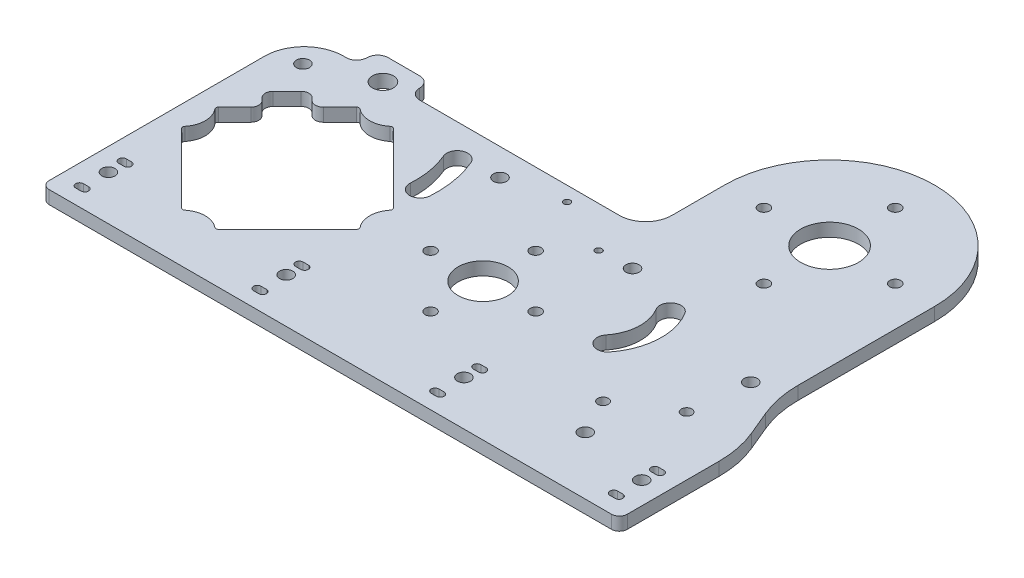
SolidWorks part; units mm, degrees
material "6061 Alloy"
ref_plane "Front Plane" through (0, 0, 0) normal (0, 0, 1) x (1, 0, 0)
ref_plane "Top Plane" through (0, 0, 0) normal (0, 1, 0) x (1, 0, 0)
ref_plane "Right Plane" through (0, 0, 0) normal (1, 0, 0) x (0, 0, -1)
sketch "Sketch1" plane through (0, 0, 0) normal (0, 1, 0) x (1, 0, 0)
  line L0 (0, 0) -> (190, 0)
  line L1 (210, 70) -> (210, 130)
  line L2 (130, 130) -> (130, 110)
  line L3 (120, 100) -> (15, 100)
  line L4 (0, 85) -> (0, 0)
  line L5 (41.3, 81.8789) -> (41.3, 71.8789) construction
  line L6 (41.3, 71.8789) -> (41.3, 52.3789) construction
  line L7 (41.3, 52.3789) -> (8.8, 52.3789) construction
  line L8 (17.63, 76.0489) -> (64.97, 76.0489) construction
  line L9 (17.63, 76.0489) -> (17.63, 28.7089) construction
  line L10 (17.63, 28.7089) -> (64.97, 28.7089) construction
  line L11 (64.97, 76.0489) -> (64.97, 28.7089) construction
  line L12 (17.63, 76.0489) -> (64.97, 28.7089) construction
  line L13 (17.63, 28.7089) -> (64.97, 76.0489) construction
  line L14 (190, 0) -> (0, 0)
  line L16 (220, 0) -> (190, 0)
  line L17 (220, 0) -> (220, 29.75)
  line L18 (220, 29.75) -> (220, 46)
  line L19 (220, 46) -> (210, 70)
  line L23 (0.9949, 52.3789) -> (41.3, 12.0739)
  line L24 (0.9949, 52.3789) -> (41.3, 92.684)
  line L25 (41.3, 12.0739) -> (81.6051, 52.3789)
  line L26 (41.3, 92.684) -> (81.6051, 52.3789)
  line L27 (41.3, 92.684) -> (41.3, 12.0739) construction
  line L28 (0.9949, 52.3789) -> (81.6051, 52.3789) construction
  line L29 (25.8323, 77.2163) -> (16.2985, 67.6826)
  line L30 (25.8323, 77.2163) -> (20.6243, 82.4243)
  line L31 (16.2985, 67.6826) -> (11.0905, 72.8905)
  line L32 (20.6243, 82.4243) -> (11.0905, 72.8905)
  line L34 (-5.1021, -31.4384) -> (-2.4551, -34.0854)
  arc A0 (210, 130) -> (130, 130) centre (170, 130) ccw
  arc A1 (15, 100) -> (0, 85) centre (15, 85) ccw
  arc A2 (130, 110) -> (120, 100) centre (120, 110) cw
  circle A3 centre (170, 130) radius 11
  circle A4 centre (170, 130) radius 25 construction
  circle A5 centre (170, 105) radius 2.1
  circle A9 centre (115.75, 52.3789) radius 9.5
  circle A10 centre (41.3, 52.3789) radius 19 construction
  circle A11 centre (41.3, 52.3789) radius 19.5 construction
  circle A12 centre (17.63, 76.0489) radius 2.1 construction
  circle A13 centre (64.97, 76.0489) radius 2.1 construction
  circle A14 centre (64.97, 28.7089) radius 2.1 construction
  circle A15 centre (17.63, 28.7089) radius 2.1 construction
  circle A16 centre (9.8356, 89.7253) radius 2.5
  circle A17 centre (84.8356, 89.7253) radius 2.5
  circle A18 centre (200, 70) radius 2.5
  circle A22 centre (145, 130) radius 2.1
  circle A23 centre (170, 155) radius 2.1
  circle A24 centre (195, 130) radius 2.1
  circle A25 centre (115.75, 72.3789) radius 2.1
  circle A26 centre (115.75, 52.3789) radius 9.5
  circle A27 centre (135.75, 52.3789) radius 2.1
  circle A28 centre (115.75, 52.3789) radius 9.5
  circle A29 centre (115.75, 32.3789) radius 2.1
  circle A30 centre (115.75, 52.3789) radius 9.5
  circle A31 centre (95.75, 52.3789) radius 2.1
  circle A32 centre (185, 22) radius 2.5
  circle A33 centre (140, 85) radius 2.5
  circle A35 centre (105.6349, 94.474) radius 1.25
  circle A36 centre (127.6349, 84.474) radius 1.25
  arc A37 (34.936, 86.3201) -> (47.664, 86.3201) centre (41.3, 92.684) ccw
  arc A38 (-5.1021, -31.4384) -> (0.5548, -31.4384) centre (-2.2737, -28.61) ccw
  arc A39 (75.2411, 58.7429) -> (75.2411, 46.015) centre (81.6051, 52.3789) ccw
  arc A40 (47.664, 18.4378) -> (34.936, 18.4378) centre (41.3, 12.0739) ccw
  arc A41 (7.3589, 46.015) -> (7.3589, 58.7429) centre (0.9949, 52.3789) ccw
  arc A42 (164.7755, 80.1528) -> (157.9457, 75.987) centre (161.3606, 78.0699) ccw construction
  arc A43 (156.8611, 58.0594) -> (157.9457, 75.987) centre (144.5266, 67.8022) ccw construction
  arc A44 (163.1389, 53.1007) -> (164.7755, 80.1528) centre (144.5266, 67.8022) ccw construction
  arc A45 (156.8611, 58.0594) -> (163.1389, 53.1007) centre (160, 55.58) ccw construction
  circle A46 centre (197.5923, 48) radius 2
  circle A47 centre (178.187, 35.6118) radius 2
  arc A54 (164.7755, 80.1528) -> (157.9457, 75.987) centre (161.3606, 78.0699) ccw
  arc A55 (156.8611, 58.0594) -> (157.9457, 75.987) centre (144.5266, 67.8022) ccw
  arc A56 (163.1389, 53.1007) -> (164.7755, 80.1528) centre (144.5266, 67.8022) ccw
  arc A57 (156.8611, 58.0594) -> (163.1389, 53.1007) centre (160, 55.58) ccw
  arc A66 (69.56, 70.8904) -> (66.9442, 86.0935) centre (36.4824, 73.0259) ccw construction
  arc A67 (69.56, 70.8904) -> (77.5434, 70.375) centre (73.5517, 70.6327) ccw construction
  arc A68 (74.2963, 89.2474) -> (66.9442, 86.0935) centre (70.6203, 87.6705) ccw construction
  arc A69 (77.5434, 70.375) -> (74.2963, 89.2474) centre (36.4824, 73.0259) ccw construction
  arc A70 (69.56, 70.8904) -> (66.9442, 86.0935) centre (36.4824, 73.0259) ccw
  arc A71 (69.56, 70.8904) -> (77.5434, 70.375) centre (73.5517, 70.6327) ccw
  arc A72 (74.2963, 89.2474) -> (66.9442, 86.0935) centre (70.6203, 87.6705) ccw
  arc A73 (77.5434, 70.375) -> (74.2963, 89.2474) centre (36.4824, 73.0259) ccw
  point P27 (160, 125)
  point P28 (160, 130)
  point P46 (36.3, 48)
  point P54 (170, 130)
  point P67 (115.75, 52.3789)
  point P77 (41.3, 52.3789)
  point P97 (41.3, 52.3789)
  point P118 (-8.7342, 21.5656)
  dimension "D3" = 40
  dimension "D4" = 10
  dimension "D6" = 22
  dimension "D7" = 4.2
  dimension "D9" = 19
  dimension "D10" = 38
  dimension "D17" = 22
  dimension "D18" = 4.2
  dimension "D19" = 35
  dimension "D20" = 130
  dimension "D21" = 5
  dimension "D28" = 50
  dimension "D30" = 4.2
  dimension "D39" = 4
  dimension "D42" = 2.5
  dimension "D46" = 4
  dimension "D44" = 57
  dimension "D45" = 9
  dimension "D1" = 190
  dimension "D5" = 105
  dimension "D8" = 74.45
  dimension "D11" = 41.3
  dimension "D12" = 85
  dimension "D13" = 10
  dimension "D14" = 19.5
  dimension "D15" = 47.34
  dimension "D16" = 47.34
  dimension "D22" = 7
  dimension "D23" = 75
  dimension "D24" = 10
  dimension "D25" = 70
  dimension "D27" = 30
  dimension "D29" = 94.7
  dimension "D31" = 20
  dimension "D33" = 46
  dimension "D34" = 50
  dimension "D35" = 115.75
  dimension "D36" = 52.3789
  dimension "D37" = 70
  dimension "D38" = 85
  dimension "D43" = 45
  dimension "D26" = 4
  dimension "D32" = 4
extrude "Boss-Extrude1" add sketch "Sketch1" along normal blind 5
extrude "Cut-Extrude1" cut sketch "Sketch2" against normal mid plane 200
sketch "Sketch2" plane through (300.1958, -95, 207.7966) normal (0, 1, 0) x (1, 0, 0)
  line L1 (-87.4826, 230.7966) -> (-89.4826, 230.7966) construction
  line L2 (-87.4826, 229.5466) -> (-89.4826, 229.5466)
  line L3 (-87.4826, 232.0466) -> (-89.4826, 232.0466)
  line L4 (-87.4826, 214.7966) -> (-89.4826, 214.7966) construction
  line L5 (-87.4826, 213.5466) -> (-89.4826, 213.5466)
  line L6 (-87.4826, 216.0466) -> (-89.4826, 216.0466)
  circle A0 centre (371.201, 492.148) radius 2.5
  arc A1 (-87.4826, 229.5466) -> (-87.4826, 232.0466) centre (-87.4826, 230.7966) ccw
  arc A2 (-89.4826, 232.0466) -> (-89.4826, 229.5466) centre (-89.4826, 230.7966) ccw
  arc A3 (-87.4826, 213.5466) -> (-87.4826, 216.0466) centre (-87.4826, 214.7966) ccw
  arc A4 (-89.4826, 216.0466) -> (-89.4826, 213.5466) centre (-89.4826, 214.7966) ccw
  point P7 (-88.4826, 230.7966)
  point P12 (-88.4826, 214.7966)
sketch "Sketch15" [suppressed] plane through (0, 5, 0) normal (0, 1, 0) x (1, 0, 0)
  circle A0 centre (41.3, 52.3789) radius 33.333 construction
  circle A1 centre (41.3, 85.712) radius 2
  circle A2 centre (74.633, 52.3789) radius 2
  circle A3 centre (41.3, 19.0459) radius 2
  circle A4 centre (7.967, 52.3789) radius 2
  point P14 (41.3, 52.3789)
  dimension "D1" = 4
  dimension "D2" = 4
sketch "Sketch17" [suppressed] plane through (0, 5, 0) normal (0, 1, 0) x (1, 0, 0)
  line L0 (210.7132, 23) -> (212.7132, 23) construction
  line L1 (210.7132, 24.3615) -> (212.7132, 24.3615)
  line L2 (210.7132, 21.6385) -> (212.7132, 21.6385)
  line L3 (210.7132, 7) -> (212.7132, 7) construction
  line L4 (210.7132, 8.3119) -> (212.7132, 8.3119)
  line L5 (210.7132, 5.6881) -> (212.7132, 5.6881)
  circle A0 centre (211.7132, 15) radius 2.5
  arc A1 (210.7132, 24.3615) -> (210.7132, 21.6385) centre (210.7132, 23) ccw
  arc A2 (212.7132, 21.6385) -> (212.7132, 24.3615) centre (212.7132, 23) ccw
  arc A3 (210.7132, 8.3119) -> (210.7132, 5.6881) centre (210.7132, 7) ccw
  arc A4 (212.7132, 5.6881) -> (212.7132, 8.3119) centre (212.7132, 7) ccw
  point P7 (211.7132, 23)
  point P16 (211.7132, 7)
extrude "Boss-Extrude2" [suppressed] add sketch "Sketch17" against normal blind 5
extrude "Cut-Extrude15" cut sketch "Sketch18" against normal through all
sketch "Sketch18" plane through (300.638, 0, 207.7972) normal (0, -1, 0) x (-1, 0, 0)
  line L1 (293.118, 231.1472) -> (291.118, 231.1472) construction
  line L2 (293.118, 229.6972) -> (291.118, 229.6972)
  line L3 (293.118, 232.5972) -> (291.118, 232.5972)
  line L4 (293.118, 214.7972) -> (291.118, 214.7972) construction
  line L5 (293.118, 213.3472) -> (291.118, 213.3472)
  line L6 (293.118, 216.2472) -> (291.118, 216.2472)
  line L7 (225.458, 230.7972) -> (223.458, 230.7972) construction
  line L8 (225.458, 229.3472) -> (223.458, 229.3472)
  line L9 (225.458, 232.2472) -> (223.458, 232.2472)
  line L10 (225.458, 214.7972) -> (223.458, 214.7972) construction
  line L11 (225.458, 213.3472) -> (223.458, 213.3472)
  line L12 (225.458, 216.2472) -> (223.458, 216.2472)
  line L13 (157.798, 230.7972) -> (155.798, 230.7972) construction
  line L14 (157.798, 229.3472) -> (155.798, 229.3472)
  line L15 (157.798, 232.2472) -> (155.798, 232.2472)
  line L16 (157.798, 214.7972) -> (155.798, 214.7972) construction
  line L17 (157.798, 213.3472) -> (155.798, 213.3472)
  line L18 (157.798, 216.2472) -> (155.798, 216.2472)
  line L19 (90.138, 230.7972) -> (88.138, 230.7972) construction
  line L20 (90.138, 229.3472) -> (88.138, 229.3472)
  line L21 (90.138, 232.2472) -> (88.138, 232.2472)
  line L22 (90.138, 215.1472) -> (88.138, 215.1472) construction
  line L23 (90.138, 213.6972) -> (88.138, 213.6972)
  line L24 (90.138, 216.5972) -> (88.138, 216.5972)
  circle A0 centre (292.118, 224.7972) radius 2.5
  arc A1 (293.118, 229.6972) -> (293.118, 232.5972) centre (293.118, 231.1472) ccw
  arc A2 (291.118, 232.5972) -> (291.118, 229.6972) centre (291.118, 231.1472) ccw
  arc A3 (293.118, 213.3472) -> (293.118, 216.2472) centre (293.118, 214.7972) ccw
  arc A4 (291.118, 216.2472) -> (291.118, 213.3472) centre (291.118, 214.7972) ccw
  circle A5 centre (224.458, 224.7972) radius 2.5
  arc A6 (225.458, 229.3472) -> (225.458, 232.2472) centre (225.458, 230.7972) ccw
  arc A7 (223.458, 232.2472) -> (223.458, 229.3472) centre (223.458, 230.7972) ccw
  arc A8 (225.458, 213.3472) -> (225.458, 216.2472) centre (225.458, 214.7972) ccw
  arc A9 (223.458, 216.2472) -> (223.458, 213.3472) centre (223.458, 214.7972) ccw
  circle A10 centre (156.798, 224.7972) radius 2.5
  arc A11 (157.798, 229.3472) -> (157.798, 232.2472) centre (157.798, 230.7972) ccw
  arc A12 (155.798, 232.2472) -> (155.798, 229.3472) centre (155.798, 230.7972) ccw
  arc A13 (157.798, 213.3472) -> (157.798, 216.2472) centre (157.798, 214.7972) ccw
  arc A14 (155.798, 216.2472) -> (155.798, 213.3472) centre (155.798, 214.7972) ccw
  circle A15 centre (89.138, 224.7972) radius 2.5
  arc A16 (90.138, 229.3472) -> (90.138, 232.2472) centre (90.138, 230.7972) ccw
  arc A17 (88.138, 232.2472) -> (88.138, 229.3472) centre (88.138, 230.7972) ccw
  arc A18 (90.138, 213.6972) -> (90.138, 216.5972) centre (90.138, 215.1472) ccw
  arc A19 (88.138, 216.5972) -> (88.138, 213.6972) centre (88.138, 215.1472) ccw
  point P7 (292.118, 231.1472)
  point P12 (292.118, 214.7972)
  point P26 (224.458, 230.7972)
  point P31 (224.458, 214.7972)
  point P42 (156.798, 230.7972)
  point P47 (156.798, 214.7972)
  point P58 (89.138, 230.7972)
  point P63 (89.138, 215.1472)
  dimension "D1" = 1.45
fillet "Fillet2" radius 40 1 edges at (210, 2.5, -70)
fillet "Fillet3" radius 40 1 edges at (220, 2.5, -46)
extrude "Cut-Extrude16" cut sketch "Sketch19" against normal through all
sketch "Sketch19" plane through (300.1958, 5, 207.7966) normal (0, 1, 0) x (1, 0, 0)
  line L0 (-265.3517, 298.1022) -> (-261.5739, 294.3244)
  line L1 (-293.2736, 270.1803) -> (-265.3517, 298.1022)
  line L2 (-293.3814, 257.1607) -> (-265.4596, 229.2388)
  line L3 (-252.3321, 297.9943) -> (-224.4102, 270.0725)
  line L4 (-252.44, 229.131) -> (-224.5181, 257.0528)
  line L5 (-299.6216, 263.6166) -> (-217.7387, 263.6166) construction
  line L6 (-258.764, 304.5642) -> (-259.0276, 222.7011) construction
  line L9 (-256.112, 294.2186) -> (-252.3321, 297.9943)
  line L11 (-228.2938, 260.8327) -> (-224.5181, 257.0528)
  line L12 (-224.4102, 270.0725) -> (-228.188, 266.2947)
  line L14 (-261.6797, 233.0145) -> (-265.4596, 229.2388)
  line L15 (-252.44, 229.131) -> (-256.2177, 232.9088)
  line L16 (-289.4979, 266.4004) -> (-293.2736, 270.1803)
  line L17 (-293.3814, 257.1607) -> (-289.6036, 260.9385)
  arc A1 (-261.5739, 294.3244) -> (-256.112, 294.2186) centre (-258.788, 297.1103) ccw
  arc A2 (-228.188, 266.2947) -> (-228.2938, 260.8327) centre (-225.4021, 263.5087) ccw
  arc A3 (-256.2177, 232.9088) -> (-261.6797, 233.0145) centre (-259.0037, 230.1228) ccw
  arc A4 (-289.6036, 260.9385) -> (-289.4979, 266.4004) centre (-292.3896, 263.7244) ccw
  point P3 (-258.8958, 263.6166)
  point P39 (-258.8958, 263.6166)
sketch "Sketch21" plane through (0, 5, 0) normal (0, 1, 0) x (1, 0, 0)
  line L0 (120, 100) -> (15, 100) construction
  line L1 (40, 100) -> (20, 100)
  line L2 (40, 100) -> (40, 108)
  line L3 (40, 108) -> (20, 108)
  line L4 (20, 100) -> (20, 108)
  dimension "D1" = 5
  dimension "D2" = 20
  dimension "D3" = 8
extrude "Boss-Extrude3" add sketch "Sketch21" against normal blind 5
sketch "Sketch20" plane through (0, 0, 0) normal (0, -1, 0) x (-1, 0, 0)
  line L0 (-60.8, 52.3789) -> (-106.25, 52.3789) construction
  line L1 (-83.525, 52.3789) -> (-83.525, 69.9739) construction
  line L2 (-120, 100) -> (-40, 100) construction
  line L3 (0, 85) -> (0, 0) construction
  circle A0 centre (-31, 99) radius 4
  circle A1 centre (-115.75, 52.3789) radius 9.5 construction
  dimension "D5" = 1
  dimension "D6" = 31
  dimension "D7" = 8
extrude "Cut-Extrude17" cut sketch "Sketch20" against normal through all
fillet "Fillet5" radius 1 8 edges at (75.2411, 2.5, -58.7429) (75.2411, 2.5, -46.015) (47.664, 2.5, -18.4378) (34.936, 2.5, -18.4378) (7.3589, 2.5, -46.015) (7.3589, 2.5, -58.7429) (47.664, 2.5, -86.3201) (34.936, 2.5, -86.3201)
fillet "Fillet6" radius 3 4 edges at (16.2985, 2.5, -67.6826) (11.0905, 2.5, -72.8905) (20.6243, 2.5, -82.4243) (25.8323, 2.5, -77.2163)
fillet "Fillet7" radius 4 4 edges at (40, 2.5, -100) (40, 2.5, -108) (20, 2.5, -108) (20, 2.5, -100)
fillet "Fillet8" radius 3 2 edges at (220, 2.5, 0) (0, 2.5, 0)
